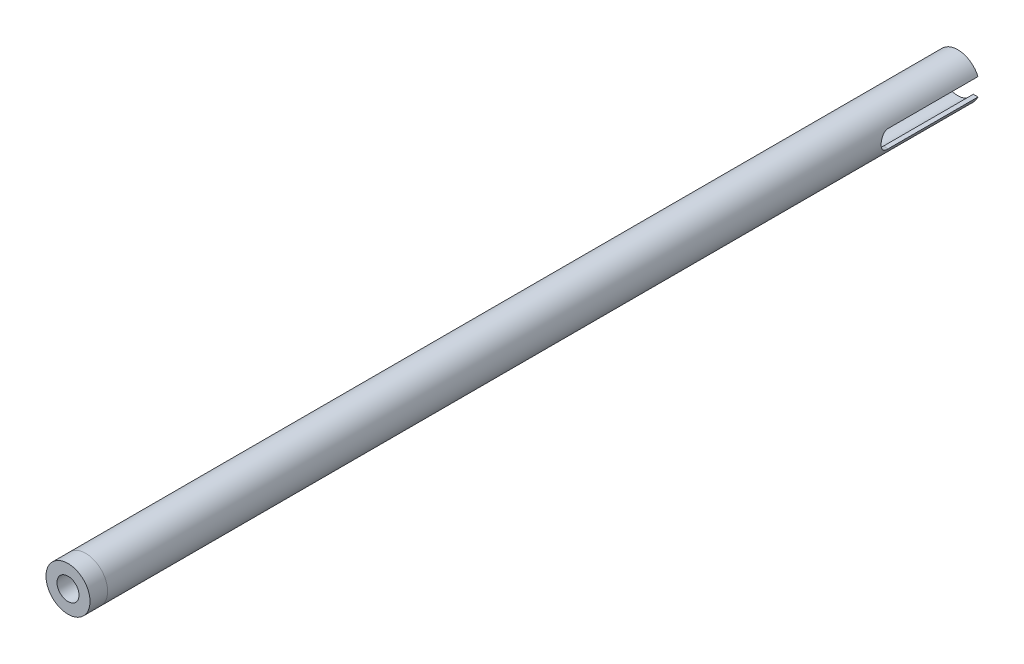
SolidWorks part; units mm, degrees
material "AISI 4130 Steel, annealed at 865C"
ref_plane "Front Plane" through (0, 0, 0) normal (0, 0, 1) x (1, 0, 0)
ref_plane "Top Plane" through (0, 0, 0) normal (0, 1, 0) x (1, 0, 0)
ref_plane "Right Plane" through (0, 0, 0) normal (1, 0, 0) x (0, 0, -1)
sketch "Axis" plane through (0, 0, 0) normal (0, 1, 0) x (1, 0, 0)
  line L0 (0, 0) -> (0, 320.6091) construction
  line L1 (0, 0) -> (0, -34.925) construction
  line L2 (0, 320.6091) -> (-7.9375, 320.6091) construction
  line L4 (0, 349.581) -> (-25.9803, 254.753) construction
  dimension "D1" = 34.925
  dimension "D2" = 7.9375
sketch "Sketch1" plane through (0, 0, 0) normal (0, 0, 1) x (1, 0, 0)
  line L0 (-7.9375, 0) -> (7.9375, 0) construction
  line L1 (-7.2748, 3.175) -> (7.2748, 3.175)
  line L2 (-7.2748, -3.175) -> (7.2748, -3.175)
  circle A0 centre (0, 0) radius 7.9375
  circle A1 centre (0, 0) radius 6.4135
  circle A2 centre (0, 0) radius 3.9688
  dimension "D1" = 15.875
  dimension "D3" = 7.9375
  dimension "D2" = 1.524
  dimension "D4" = 6.35
extrude "Threaded insert 1-1" add sketch "Sketch1" against normal blind 6.35 contours A2 L1 A1 | A1 L1 A0 | A2 L0 A1 L1 | A1 L0 A0 L1 | L0 A1 L2 A0 | L0 A2 L2 A1 | A2 L2 A1 | A1 L2 A0 | L0 A1 L2 A2 | L0 A0 L2 A1 | A0 L0 A1 L1 | A1 L0 A2 L1 region at (4.7887, 1.6543, 0) region at (4.7887, -1.6543, 0) region at (6.9234, 1.6163, 0) region at (6.9234, -1.6163, 0) region at (-4.7887, -1.6543, 0) region at (-4.7887, 1.6543, 0) region at (0, 4.6159, 0) region at (0, -4.6159, 0) region at (0, 6.5666, 0) region at (6.4237, -3.3281, 0) region at (-6.9234, -1.6163, 0) region at (-6.9234, 1.6163, 0)
extrude "Threaded insert 1-2" add sketch "Sketch1<3>" against normal blind 9.525 from surface contours A2 L1 A1 | A2 L0 A1 L1 | L0 A2 L2 A1 | A2 L2 A1 | L0 A1 L2 A2 | A1 L0 A2 L1 region at (4.7887, 1.6543, 0) region at (4.7887, -1.6543, 0) region at (-4.7887, -1.6543, 0) region at (-4.7887, 1.6543, 0) region at (0, 4.6159, 0) region at (0, -4.6159, 0) starting at face at (7.9375, 0, -6.35)
sketch "Sketch1<3>" plane through (0, 0, 0) normal (0, 0, 1) x (1, 0, 0) same geometry as "Sketch1"
extrude "A-arm tube" add sketch "Sketch1<4>" against normal up to vertex (320.6091 mm away) from surface separate body contours A1 L1 A0 | A1 L0 A0 L1 | L0 A1 L2 A0 | A1 L2 A0 | L0 A0 L2 A1 | A0 L0 A1 L1 region at (6.9234, 1.6163, 0) region at (6.9234, -1.6163, 0) region at (0, 6.5666, 0) region at (6.4237, -3.3281, 0) region at (-6.9234, -1.6163, 0) region at (-6.9234, 1.6163, 0) up to point (0, 0, -320.6091) starting at face at (6.4135, 0, -6.35)
sketch "Sketch1<4>" plane through (0, 0, 0) normal (0, 0, 1) x (1, 0, 0) same geometry as "Sketch1"
extrude "Apex slot" cut sketch "Sketch1<5>" along normal blind 35.56 from surface contours A0 L0 A1 L1 | L0 A0 L2 A1 | A1 L0 A0 L1 | L0 A1 L2 A0 region at (6.9234, 1.6163, 0) region at (6.9234, -1.6163, 0) region at (-6.9234, -1.6163, 0) region at (-6.9234, 1.6163, 0) starting at face at (6.4135, 0, -320.6091)
sketch "Sketch1<5>" plane through (0, 0, 0) normal (0, 0, 1) x (1, 0, 0) same geometry as "Sketch1"
fillet "Fillet1" radius 3.175 4 edges at (-6.4237, 3.175, -285.0491) (-6.4237, -3.175, -285.0491) (6.4237, -3.175, -285.0491) (6.4237, 3.175, -285.0491)
equation "\"tube diameter\"= 5 / 8"
equation "\"tube thickness\"= .06"
equation "\"apex thickness\"= .25"
equation "\"tube slot\"= 1.4"
equation "\"D1@Sketch1\"=\"tube diameter\""
equation "\"D2@Sketch1\"=\"tube thickness\""
equation "\"threaded insert hole\"= .3125"
equation "\"D3@Sketch1\"=\"threaded insert hole\""
equation "\"D4@Sketch1\"=\"apex thickness\""
equation "\"D1@Apex slot\" = \"tube slot\""
equation "\"D1@Fillet1\"=\"apex thickness\"/2"
equation "\"D2@Axis\"=\"tube diameter\"/2"
